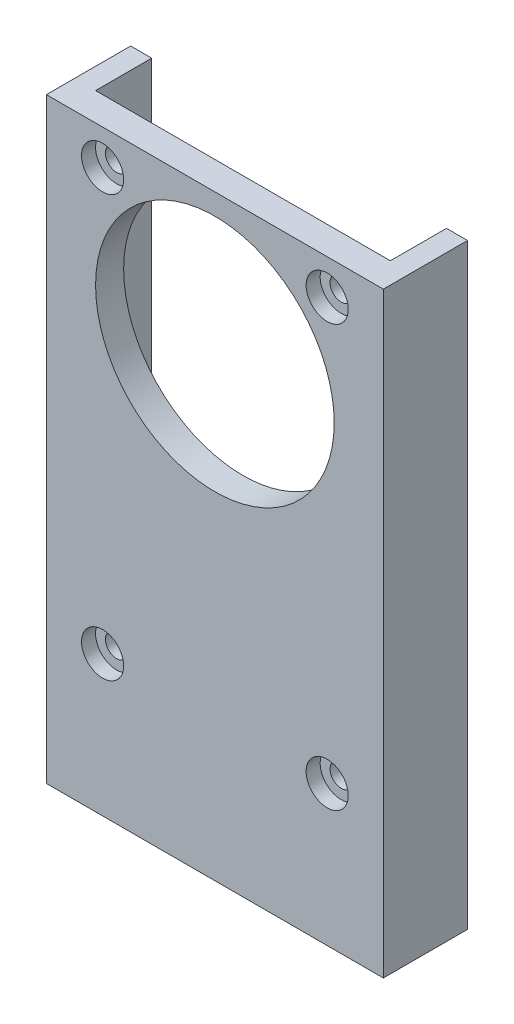
SolidWorks part; units mm, degrees
ref_plane "Front Plane" through (0, 0, 0) normal (0, 0, 1) x (1, 0, 0)
ref_plane "Top Plane" through (0, 0, 0) normal (0, 1, 0) x (1, 0, 0)
ref_plane "Right Plane" through (0, 0, 0) normal (1, 0, 0) x (0, 0, -1)
sketch "Sketch1" plane through (0, 0, 0) normal (0, 0, 1) x (1, 0, 0)
  line L1 (-10.5, -17.5) -> (10.5, -17.5)
  line L2 (-10.5, -17.5) -> (-10.5, 17.5)
  line L3 (-10.5, 17.5) -> (10.5, 17.5)
  line L4 (10.5, -17.5) -> (10.5, 17.5)
  line L5 (0, 17.5) -> (0, -17.5) construction
  line L6 (-10.5, 0) -> (10.5, 0) construction
  circle A0 centre (-8, 15) radius 0.8
  circle A1 centre (8, 15) radius 0.8
  circle A2 centre (8, -15) radius 0.8
  circle A3 centre (-8, -15) radius 0.8
  circle A4 centre (0, 7.5) radius 8.5
  point P0 (0, 0)
  dimension "D5" = 1.6
  dimension "D7" = 17
  dimension "D1" = 35
  dimension "D2" = 21
  dimension "D3" = 8
  dimension "D4" = 15
  dimension "D6" = 7.5
extrude "BracketWithBoltHoles" add sketch "Sketch1" along normal blind 2 contours L2 L1 L4 L3 A1 A0 A2 A3 region at (0, -3.4049, 0)
sketch "Sketch2" plane through (0, 0, 2) normal (0, 0, 1) x (1, 0, 0)
  line L1 (-10.5, -17.5) -> (10.5, -17.5)
  line L2 (-10.5, -17.5) -> (-10.5, -25)
  line L3 (-10.5, -25) -> (10.5, -25)
  line L4 (10.5, -17.5) -> (10.5, -25)
  line L5 (-5, -25) -> (5, -25)
  line L6 (-5, -25) -> (-5, -23)
  line L7 (-5, -23) -> (5, -23)
  line L8 (5, -25) -> (5, -23)
  line L9 (0, -23) -> (0, -25) construction
  line L10 (-5, -24) -> (5, -24) construction
  circle A0 centre (8, 15) radius 0.8 construction
  circle A1 centre (8, 15) radius 0.8 construction
  point P8 (0, -24)
  point P15 (0, -25)
  line M8 (-10.5, -17.5) -> (10.5, -17.5)
  dimension "D1" = 40
  dimension "D2" = 10
  dimension "D3" = 2
extrude "BracketExtension" add sketch "Sketch2" against normal up to surface (2 mm away) contours L8 L3 L4 L2 L6 L7 M8 | L3 L8 L7 L6 region at (0, -20.85, 2) region at (0, -24, 2) up to face at (8.5, 7.5, 0)
extrude "Base" add sketch "Sketch2<3>" against normal blind 7.5 contours L3 L8 L7 L6 region at (0, -24, 2)
sketch "Sketch2<3>" plane through (0, 0, 2) normal (0, 0, 1) x (1, 0, 0) same geometry as "Sketch2"
sketch "Sketch3" plane through (0, -23, 0) normal (0, 1, 0) x (1, 0, 0)
  line L0 (0, 5.5) -> (0, 0) construction
  line L1 (-5, 5.5) -> (5, 5.5) construction
  line L3 (-10.5, -1) -> (10.5, -1) construction
  line L4 (-10.5, -2) -> (-10.5, 0) construction
  line L5 (10.5, -2) -> (10.5, 0) construction
  line L11 (2.3094, 2.75) -> (1.1547, 4.75)
  line L12 (1.1547, 4.75) -> (-1.1547, 4.75)
  line L13 (-1.1547, 4.75) -> (-2.3094, 2.75)
  line L14 (-2.3094, 2.75) -> (-1.1547, 0.75)
  line L15 (-1.1547, 0.75) -> (1.1547, 0.75)
  line L16 (1.1547, 0.75) -> (2.3094, 2.75)
  circle A0 centre (0, 2.75) radius 1
  circle A1 centre (0, 2.75) radius 2 construction
  dimension "D2" = 4
extrude "BaseBoltHole" cut sketch "Sketch3" against normal through all contours A0 region at (0, -23, -2.75)
extrude "BaseNutSlot" cut sketch "Sketch3<3>" against normal blind 1 contours L15 L16 L11 L12 L13 L14 A0 region at (1.6791, -23, -1.7806)
sketch "Sketch3<3>" plane through (0, -23, 0) normal (0, 1, 0) x (1, 0, 0) same geometry as "Sketch3"
sketch "Sketch4" plane through (0, 17.5, 0) normal (0, 1, 0) x (1, 0, 0)
  line L0 (-10.5, -2) -> (-10.5, 0) construction
  line L5 (-12, 4) -> (-10.5, 4)
  line L6 (-12, 4) -> (-12, -6)
  line L7 (-12, -6) -> (-10.5, -6)
  line L8 (-10.5, 4) -> (-10.5, -6)
  line L9 (-11.25, -6) -> (-11.25, 4) construction
  line L10 (-12, -1) -> (-10.5, -1) construction
  line L11 (-10.5, -2) -> (-10.5, 0) construction
  line L12 (-10.5, -2) -> (-12, -2)
  point P0 (-11.25, -1)
  point P9 (-10.5, -1)
  line M4 (-10.5, 0) -> (-10.5, -2)
  dimension "D1" = 1.5
  dimension "D2" = 10
extrude "StiffenerRib" add sketch "Sketch4" against normal up to surface (42.5 mm away) contours L12 L8 L5 L6 M4 region at (-11.25, 17.5, -1) up to face at (0, -25, -1.75)
mirror "StiffenerRib2" about plane through (0, 0, 0) normal (1, 0, 0) of "StiffenerRib"
sketch "Sketch5" plane through (0, 0, 2) normal (0, 0, 1) x (1, 0, 0)
  line L0 (0, 0) -> (0, 6.1378) construction
  circle A0 centre (8, -15) radius 0.8 construction
  circle A1 centre (8, 15) radius 0.8 construction
  circle A2 centre (8, -15) radius 0.8 construction
  circle A3 centre (8, 15) radius 0.8 construction
  circle A4 centre (8, 15) radius 1.5
  circle A5 centre (8, -15) radius 1.5
  circle A6 centre (-8, -15) radius 1.5
  circle A7 centre (-8, 15) radius 1.5
  dimension "D2" = 3
extrude "BoltHatSlots" cut sketch "Sketch5" against normal blind 1
equation "\"BoltD\"=2mm"
equation "\"BoltHatD\"=3.2mm"
equation "\"NutShortSide\"=4mm"
equation "\"NutLongSide\"=4.5mm"
equation "\"SmallScrewD\"=1.2mm"
equation "\"SmallScrewHatD\"=2mm"
equation "\"TubeOuterD\"=1.2mm"
equation "\"TubeClipW\"=1.5mm"
equation "\"TubeClipH\"=1.5mm"
equation "\"TubeClipLock_SideL\"=1.5mm"
equation "\"TubeClipLock_W\"=0.7mm"
equation "\"BasicPulleyD\"=15mm"
equation "\"GrooveDepth\"=0.7mm"
equation "\"Cable1D\"=0.4mm"
equation "\"Cable2D\"=0.3mm"
equation "\"BallBearingInnerD\"=2mm"
equation "\"BallBearingOuterD\"=4mm"
equation "\"BallBearingThickness\"=2mm"
equation "\"BearingCapD\"=12mm"
equation "\"HumerusL\"=37.2mm"
equation "\"HumerusElbowSidePulleyD\"=10mm"
equation "\"RadiusL\"=68.1mm"
equation "\"Finger1L\"=120mm"
equation "\"Finger2L\"=100mm"
equation "\"Finger3L\"=80mm"
equation "\"ElbowExtendedAngle\"=140deg"
equation "\"ElbowFlexedAngle\"=38deg"
equation "\"Digit5ExtendedAngle\"=80deg"
equation "\"Digit5FlexedAngle\"=24deg"
equation "\"Digit4ExtendedAngle\"=108deg"
equation "\"Digit4FlexedAngle\"=34deg"
equation "\"Digit3ExtendedAngle\"=145deg"
equation "\"Digit3FlexedAngle\"=44deg"
equation "\"KST_ServoBoltShelfHeight\"=21.1mm"
equation "\"KST_ServoLength\"=23mm"
equation "\"KST_ServoWidth\"=12mm"
equation "\"KST_ServoBoltHole2HoleLength\"=28mm"
equation "\"KST_ServoBoltHole2ShaftDist\"=8.3mm"
equation "\"KST_ServoBoltHole2HoleWidth\"=7mm"
equation "\"KST_ServoHeight\"=27.5mm"
equation "\"KST_ServoShaftHeight\"=3.5mm"
equation "\"KST_ServoShaftD\"=4.25mm"
equation "\"KST_ServoShaftToothL\"=0.345mm"
equation "\"KST_ServoShaftToothAngle\"=60deg"
equation "\"KST_ServoShaftToothTipWidth\"=0.18mm"
equation "\"KST_ServoShaftToothFilletR\"=0.1mm"
equation "\"KST_ServoShaftToothN\"=25"
equation "\"KST_ServoShaftBoltD\"=2mm"
equation "\"KST_ServoShaftBoltHatD\"=5mm"
equation "\"XL330_M077_T_Length\"=34mm"
equation "\"XL330_M077_T_Width\"=20mm"
equation "\"XL330_M077_T_Height\"=23mm"
equation "\"XL330_M077_T_BoltHole2HoleLength\"=30mm"
equation "\"XL330_M077_T_BoltHole2HoleWidth\"=16mm"
equation "\"XL330_M077_T_BoltHole2ShaftDist\"=7.5mm"
equation "\"XL330_M077_T_HornHeight\"=3mm"
equation "\"XL330_M077_T_HornScrewHoleCircleD\"=12mm"
equation "\"D1@Sketch1\"=\"XL330_M077_T_Length\"+1"
equation "\"D2@Sketch1\"=\"XL330_M077_T_Width\"+1"
equation "\"D3@Sketch1\"=\"XL330_M077_T_BoltHole2HoleWidth\"/2"
equation "\"D4@Sketch1\"=\"XL330_M077_T_BoltHole2HoleLength\"/2"
equation "\"D1@Sketch2\"=\"XL330_M077_T_BoltHole2ShaftDist\"+32.5"
equation "\"D1@Sketch3\"=\"BoltD\""
equation "\"XL330_M077_T_BoltD\"=1.6mm"
equation "\"D5@Sketch1\"=\"XL330_M077_T_FrameBoltD\""
equation "\"XL330_M077_T_HornD\"=16mm"
equation "\"D6@Sketch1\"=\"XL330_M077_T_BoltHole2ShaftDist\""
equation "\"D7@Sketch1\"=\"XL330_M077_T_HornD\"+1"
equation "\"XL330_M077_T_FrameBoltD\"=1.6mm"
equation "\"XL330_M077_T_FrameBoltHatD\"=3mm"
equation "\"XL330_M077_T_FrameNutShortSide\"=2.5mm"
equation "\"XL330_M077_T_FrameNutLongSide\"=3mm"
equation "\"XL330_M077_T_HornScrewD\"=1.9mm"
equation "\"XL330_M077_T_HornScrewHatD\"=3.3mm"
equation "\"D2@Sketch3\"=\"NutShortSide\""
equation "\"D1@Sketch5\"=\"XL330_M077_T_FrameBoltHatD\""
equation "\"D2@Sketch5\"=\"D1@Sketch5\""
